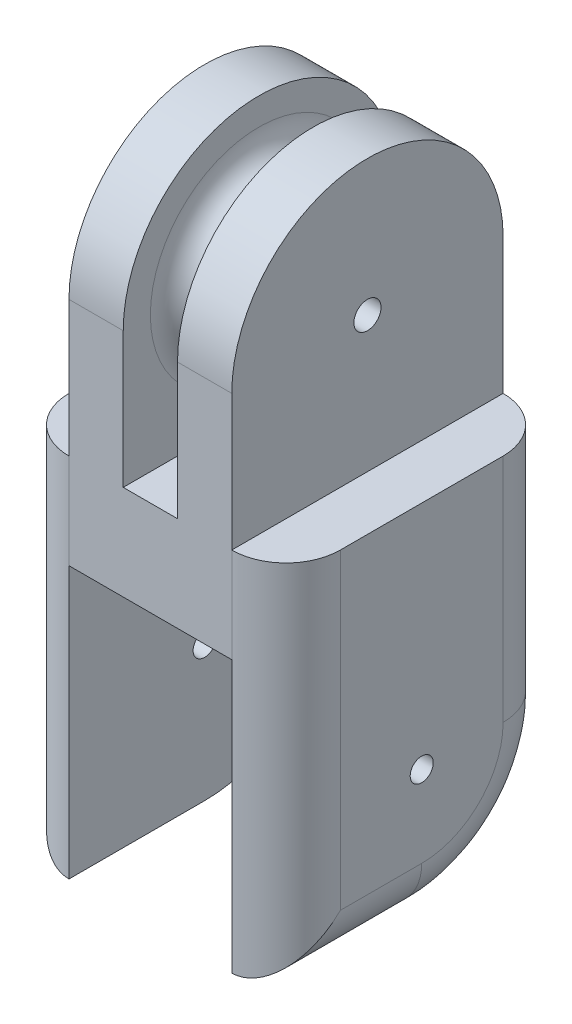
SolidWorks part; units mm, degrees
ref_plane "Front Plane" through (0, 0, 0) normal (0, 0, 1) x (1, 0, 0)
ref_plane "Top Plane" through (0, 0, 0) normal (0, 1, 0) x (1, 0, 0)
ref_plane "Right Plane" through (0, 0, 0) normal (1, 0, 0) x (0, 0, -1)
sketch "Sketch1" plane through (0, 0, 0) normal (0, 1, 0) x (1, 0, 0)
  line L0 (10, 10) -> (-10, -10) construction
  line L1 (-10, 10) -> (10, 10)
  line L2 (-10, 10) -> (-10, -10)
  line L3 (-10, -10) -> (10, -10)
  line L4 (10, 10) -> (10, -10)
  line L5 (-10, 10) -> (10, -10) construction
  point P5 (0, 0)
  dimension "D1" = 20
  dimension "D2" = 20
extrude "Boss-Extrude1" add sketch "Sketch1" along normal blind 7
sketch "Sketch4" plane through (0, 0, 0) normal (0, -1, 0) x (1, 0, 0)
  line L0 (10, -10) -> (-10, -10) construction
  line L1 (-10, 10) -> (-6, 10)
  line L2 (-10, 10) -> (-10, -10)
  line L3 (-10, -10) -> (-6, -10)
  line L4 (-6, 10) -> (-6, -10)
  line L5 (-10, 10) -> (10, 10) construction
  line L6 (10, -10) -> (6, -10)
  line L7 (10, -10) -> (10, 10)
  line L8 (10, 10) -> (6, 10)
  line L9 (6, -10) -> (6, 10)
  dimension "D1" = 4
  dimension "D2" = 4
extrude "Boss-Extrude2" add sketch "Sketch4" along normal blind 10
sketch "Sketch5" plane through (-10, 0, 0) normal (-1, 0, 0) x (0, 0, 1)
  line L0 (10, -10) -> (-10, -10) construction
  line L4 (0, -20) -> (10, -20)
  line L5 (10, -10) -> (10, -20)
  arc A0 (10, -10) -> (0, -20) centre (0, -10) ccw
extrude "Boss-Extrude3" add sketch "Sketch5" against normal blind 4
sketch "Sketch6" plane through (10, 0, 0) normal (1, 0, 0) x (0, 0, -1)
  line L0 (10, -10) -> (-10, -10) construction
  line L4 (0, -20) -> (-10, -20)
  line L5 (-10, -10) -> (-10, -20)
  arc A0 (0, -20) -> (-10, -10) centre (0, -10) ccw
extrude "Boss-Extrude4" add sketch "Sketch6" against normal blind 4
sketch "Sketch7" plane through (-10, 0, 0) normal (-1, 0, 0) x (0, 0, 1)
  circle A0 centre (0, -10) radius 0.85
  dimension "D1" = 1.7
extrude "Cut-Extrude1" cut sketch "Sketch7" against normal through all
fillet "Fillet1" radius 4 8 edges at (-10, -6.5, 10) (-10, -17.0711, -7.0711) (10, -6.5, 10) (10, -17.0711, -7.0711) (-10, -1.5, -10) (10, -1.5, -10) (10, -20, 5) (-10, -20, 5)
sketch "Sketch8" plane through (0, 7, 0) normal (0, 1, 0) x (1, 0, 0)
  line L0 (6, 10) -> (-6, 10) construction
  line L1 (6, -10) -> (2, -10)
  line L2 (6, -10) -> (6, 10)
  line L3 (6, 10) -> (2, 10)
  line L4 (2, -10) -> (2, 10)
  line L5 (-10, 6) -> (-10, -6) construction
  line L6 (-6, -10) -> (-2, -10)
  line L7 (-6, -10) -> (-6, 10)
  line L8 (-6, 10) -> (-2, 10)
  line L9 (-2, -10) -> (-2, 10)
  line L10 (10, -6) -> (10, 6) construction
  dimension "D1" = 4
  dimension "D2" = 4
  dimension "D3" = 4
  dimension "D4" = 4
extrude "Boss-Extrude5" add sketch "Sketch8" along normal blind 10
sketch "Sketch9" plane through (6, 0, 0) normal (1, 0, 0) x (0, 0, -1)
  line L0 (-10, 17) -> (10, 17) construction
  circle A0 centre (0, 17) radius 10
extrude "Boss-Extrude6" add sketch "Sketch9" against normal blind 4
sketch "Sketch10" plane through (-6, 0, 0) normal (-1, 0, 0) x (0, 0, 1)
  line L0 (-10, 17) -> (10, 17) construction
  circle A0 centre (0, 17) radius 10
extrude "Boss-Extrude7" add sketch "Sketch10" against normal blind 4
sketch "Sketch12" plane through (-6, 0, 0) normal (-1, 0, 0) x (0, 0, 1)
  circle A0 centre (0, 17) radius 1
  dimension "D1" = 2
extrude "Cut-Extrude2" cut sketch "Sketch12" against normal through all
sketch "Sketch13" plane through (-2, 0, 0) normal (1, 0, 0) x (0, 0, -1)
  circle A0 centre (0, 17) radius 6
  dimension "D1" = 12
sketch "Sketch14" plane through (-2, 0, 0) normal (1, 0, 0) x (0, 0, -1)
  circle A0 centre (0, 17) radius 3.5
  dimension "D1" = 7
extrude "Boss-Extrude8" add sketch "Sketch13" along normal blind 4
extrude "Cut-Extrude3" cut sketch "Sketch14" along normal blind 4
fillet "Fillet2" radius 2 2 edges at (2, 17, -6) (-2, 17, 6)
sketch "Sketch16" plane through (0, 0, 0) normal (0, -1, 0) x (1, 0, 0)
  line L0 (6, -10) -> (-6, -10) construction
  line L1 (-6, 0) -> (6, 0) construction
  line L2 (-6, -10) -> (-6, 10) construction
  line L3 (6, 10) -> (6, -10) construction
  circle A0 centre (0, -6) radius 0.5
  circle A1 centre (0, 6) radius 0.5
  dimension "D1" = 1
  dimension "D2" = 4
extrude "Cut-Extrude4" cut sketch "Sketch16" against normal up to next
